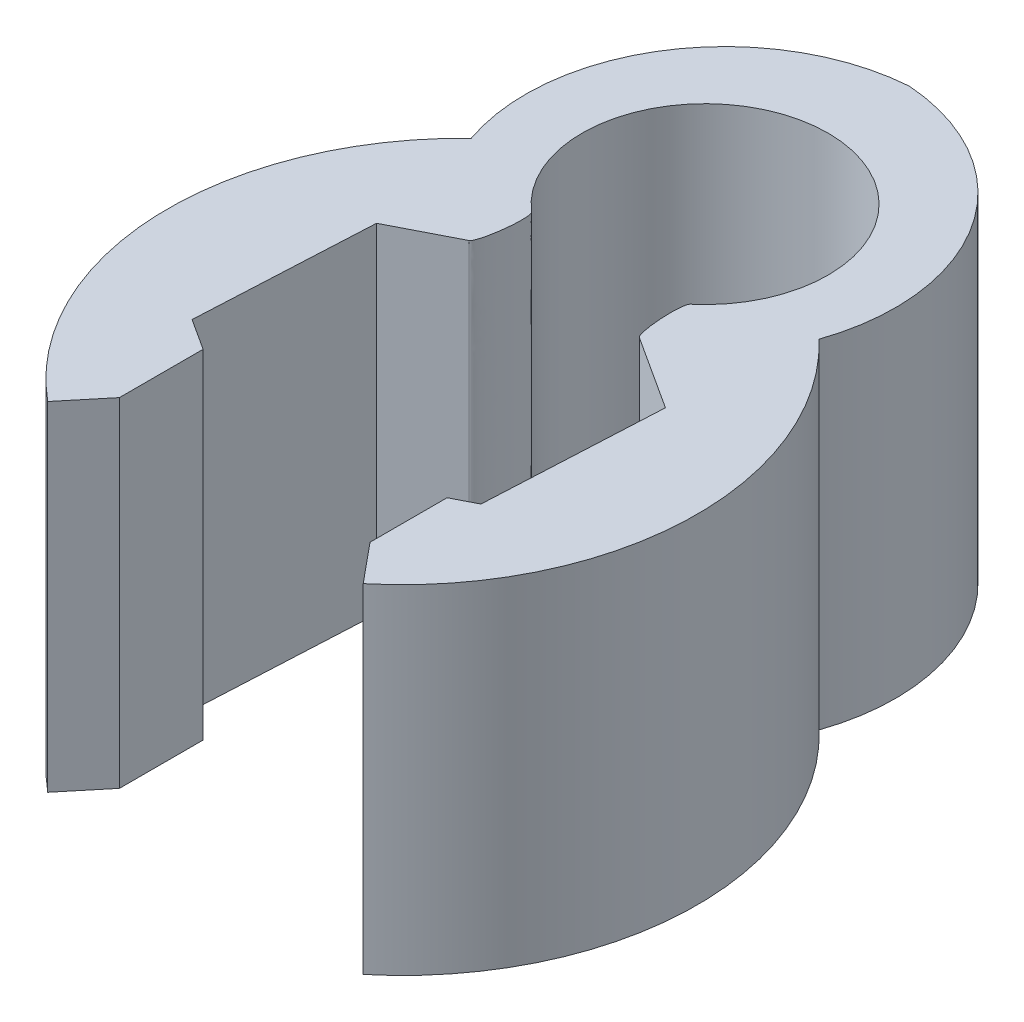
SolidWorks part; units mm, degrees
ref_plane "Front Plane" through (0, 0, 0) normal (0, 0, 1) x (1, 0, 0)
ref_plane "Top Plane" through (0, 0, 0) normal (0, 1, 0) x (1, 0, 0)
ref_plane "Right Plane" through (0, 0, 0) normal (1, 0, 0) x (0, 0, -1)
sketch "Sketch3" plane through (0, 0, 0) normal (0, 1, 0) x (1, 0, 0)
  line L0 (-7.2765, 0.1114) -> (11.8281, 0.1114) construction
  line L1 (-2.4796, 5.151) -> (-2.4796, 6.4742)
  line L2 (5.874, 3.0075) -> (0.3324, 6.5907)
  line L3 (0.3324, 6.5907) -> (-5.5415, 3.5833)
  line L4 (-5.5415, 3.5833) -> (-5.874, -3.0075)
  line L5 (-5.874, -3.0075) -> (-0.3324, -6.5907)
  line L6 (-0.3324, -6.5907) -> (5.5415, -3.5833)
  line L7 (5.5415, -3.5833) -> (5.874, 3.0075)
  line L8 (2.4796, 5.151) -> (2.4796, 6.4742)
  line L9 (-4.7012, -3.7658) -> (-4.7012, -6.9056)
  line L10 (-4.7012, -6.9056) -> (-5.9188, -8.3785)
  line L11 (0, 2.9063) -> (0, -1.8101) construction
  line L12 (4.7012, -6.9056) -> (5.9188, -8.3785)
  line L13 (4.7012, -3.7658) -> (4.7012, -6.9056)
  circle A0 centre (0, 0) radius 5.715 construction
  circle A1 centre (0, 10.3692) radius 4.6174
  arc A2 (-5.9188, -8.3785) -> (-6.5266, 8.121) centre (1.1246, 0.1419) cw
  arc A3 (-6.5266, 8.121) -> (0, 18.035) centre (0.5425, 10.5725) cw
  arc A4 (6.5266, 8.121) -> (0, 18.035) centre (-0.5425, 10.5725) ccw
  arc A5 (5.9188, -8.3785) -> (6.5266, 8.121) centre (-1.1246, 0.1419) ccw
  dimension "D1" = 11.43
  dimension "D2" = 0
extrude "Boss-Extrude1" add sketch "Sketch3" along normal blind 12.7 contours L12 A5 A4 A3 A2 L10 L9 L5 L4 L3 L1 A1 L8 L2 L7 L6 L13 | A1 L1 L3 | A1 L2 L8 region at (-4.1612, 0, -4.6613) region at (-2.0247, 0, -5.8096) region at (2.1055, 0, -5.8575)
fillet "Fillet6" radius 1.27 2 edges at (1.328, 6.35, -5.947) (-1.0635, 6.35, -5.876) conic radius 6.35
sketch "Sketch4" plane through (0, 12.7, 0) normal (0, 1, 0) x (1, 0, 0)
  line L1 (-6.1573, 3.9814) -> (-6.5266, -3.3416)
  line L2 (-6.5266, -3.3416) -> (-0.3694, -7.323)
  line L3 (-0.3694, -7.323) -> (6.1573, -3.9814)
  line L4 (6.1573, -3.9814) -> (6.5266, 3.3416)
  line L5 (6.5266, 3.3416) -> (0.3694, 7.323)
  line L6 (0.3694, 7.323) -> (-6.1573, 3.9814)
  circle A0 centre (0, 0) radius 6.35 construction
